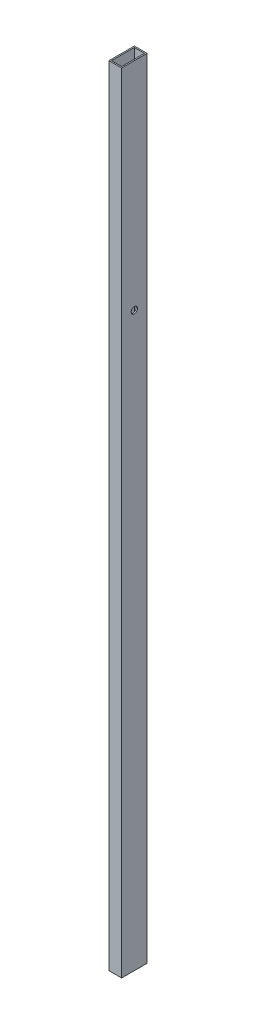
SolidWorks part; units mm, degrees
ref_plane "Спереди" through (0, 0, 0) normal (0, 0, 1) x (1, 0, 0)
ref_plane "Сверху" through (0, 0, 0) normal (0, 1, 0) x (1, 0, 0)
ref_plane "Справа" through (0, 0, 0) normal (1, 0, 0) x (0, 0, -1)
sketch "Эскиз1" plane through (0, 0, 0) normal (0, 1, 0) x (1, 0, 0)
  line L1 (-10, 20) -> (10, 20)
  line L2 (-10, 20) -> (-10, -20)
  line L3 (-10, -20) -> (10, -20)
  line L4 (10, 20) -> (10, -20)
  line L5 (-10, 20) -> (10, -20) construction
  line L6 (-10, -20) -> (10, 20) construction
  point P0 (0, 0)
extrude "Вытянуть-Тонкостенный1" add sketch "Эскиз1" along normal blind 1240 thin thin type one direction reverse wall 2
sketch "Эскиз2" plane through (10, 0, 0) normal (1, 0, 0) x (0, 0, -1)
  circle A0 centre (0, 900) radius 5
extrude "Вырез-Вытянуть1" cut sketch "Эскиз2" against normal through all
sketch "Эскиз3" plane through (-10, 0, 0) normal (-1, 0, 0) x (0, 0, 1)
  circle A0 centre (0, 720) radius 5
  circle A1 centre (0, 580) radius 5
  circle A2 centre (0, 440) radius 5
  dimension "D1" = 3
extrude "Вырез-Вытянуть2" cut sketch "Эскиз3" against normal blind 10
